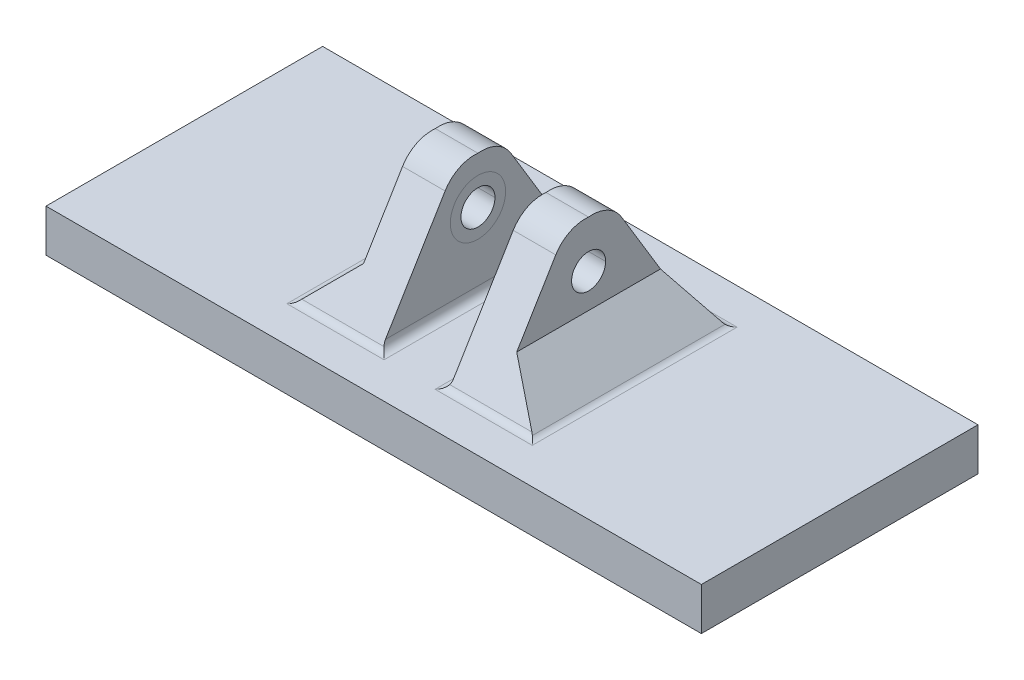
SolidWorks part; units mm, degrees
material "Onyx"
ref_plane "Front Plane" through (0, 0, 0) normal (0, 0, 1) x (1, 0, 0)
ref_plane "Top Plane" through (0, 0, 0) normal (0, 1, 0) x (1, 0, 0)
ref_plane "Right Plane" through (0, 0, 0) normal (1, 0, 0) x (0, 0, -1)
sketch "Sketch1" plane through (0, 0, 0) normal (0, 1, 0) x (1, 0, 0)
  line L1 (77, 32.5) -> (-77, 32.5)
  line L2 (77, 32.5) -> (77, -32.5)
  line L3 (77, -32.5) -> (-77, -32.5)
  line L4 (-77, 32.5) -> (-77, -32.5)
  line L5 (77, 32.5) -> (-77, -32.5) construction
  line L6 (77, -32.5) -> (-77, 32.5) construction
  point P0 (0, 0)
  dimension "D1" = 154
  dimension "D2" = 65
extrude "Boss-Extrude1" add sketch "Sketch1" along normal blind 10
sketch "Sketch2" plane through (0, 0, 0) normal (1, 0, 0) x (0, 0, -1)
  line L1 (-22.9345, 10) -> (-7.7143, 35.1803)
  line L3 (0, 0) -> (0, 39.0224) construction
  line L4 (-22.9345, 10) -> (22.9345, 10)
  line L5 (22.9345, 10) -> (7.7143, 35.1803)
  line L6 (-32.5, 0) -> (32.5, 0) construction
  line L8 (32.5, 10) -> (-32.5, 10) construction
  circle A0 centre (0, 28) radius 4
  arc A1 (-7.7143, 35.1803) -> (0, 39.0224) centre (-0.827, 31.0173) cw
  arc A2 (7.7143, 35.1803) -> (0, 39.0224) centre (0.827, 31.0173) ccw
  point P14 (0, 10)
  dimension "D2" = 8
  dimension "D1" = 28
extrude "Boss-Extrude2" add sketch "Sketch2" along normal blind 10 from offset 8
mirror "Mirror1" about plane through (0, 0, 0) normal (1, 0, 0) of "Boss-Extrude2"
ref_plane "Plane1" through (0, 28, 0) normal (0, -1, 0) x (-1, 0, 0)
split line "Split Line1"
sketch "Sketch3" plane through (-8, 0, 0) normal (1, 0, 0) x (0, 0, -1)
  circle A0 centre (0, 28) radius 6.5
  dimension "D1" = 13
split line "Split Line2"
sketch "Sketch4" plane through (8, 0, 0) normal (-1, 0, 0) x (0, 0, 1)
  circle A0 centre (0, 28) radius 6.5
  dimension "D1" = 13
split line "Split Line3"
fillet "Fillet1" [suppressed] radius 2
chamfer "Chamfer1" distance 10 angle 45 2 edges at (18, 10, 0) (-18, 10, 0)
fillet "Fillet2" radius 2 8 edges at (8, 10, 0) (18, 10, -22.9345) (28, 10, 0) (18, 10, 22.9345) (-18, 10, 22.9345) (-8, 10, 0) (-18, 10, -22.9345) (-28, 10, 0)
